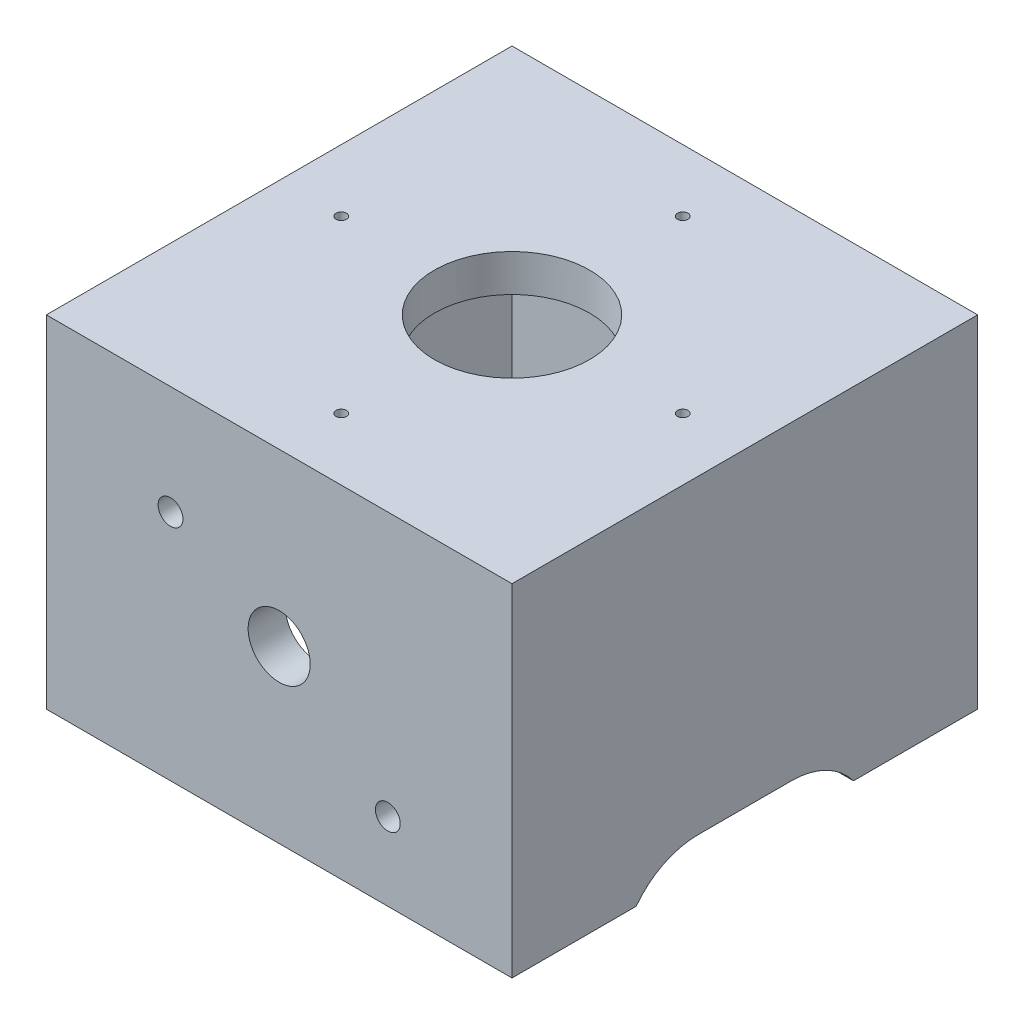
SolidWorks part; units mm, degrees
material "Teak"
ref_plane "Front Plane" through (0, 0, 0) normal (0, 0, 1) x (1, 0, 0)
ref_plane "Top Plane" through (0, 0, 0) normal (0, 1, 0) x (1, 0, 0)
ref_plane "Right Plane" through (0, 0, 0) normal (1, 0, 0) x (0, 0, -1)
sketch "Sketch1" plane through (0, 0, 0) normal (0, 1, 0) x (1, 0, 0)
  line L1 (0, 0) -> (150, 0)
  line L2 (0, 0) -> (0, 150)
  line L3 (0, 150) -> (150, 150)
  line L4 (150, 0) -> (150, 150)
  dimension "D1" = 150
  dimension "D2" = 150
extrude "Boss-Extrude1" add sketch "Sketch1" along normal blind 110
sketch "Sketch3" plane through (0, 0, 0) normal (0, -1, 0) x (1, 0, 0)
  line L14 (12, -138) -> (138, -138)
  line L15 (138, -138) -> (138, -12)
  line L16 (12, -12) -> (12, -138)
  line L17 (138, -12) -> (12, -12)
  line L18 (12, -138) -> (138, -138)
  line L19 (138, -138) -> (138, -12)
  line L20 (12, -12) -> (12, -138)
  line L21 (138, -12) -> (12, -12)
  dimension "D1" = 12
extrude "Cut-Extrude1" cut sketch "Sketch3" against normal offset from surface (98 mm away) 12 up to face at (75, 110, -75)
sketch "Sketch4" plane through (0, 110, 0) normal (0, 1, 0) x (1, 0, 0)
  line L0 (150, 0) -> (150, 150) construction
  line L1 (150, 150) -> (0, 150) construction
  line L2 (0, 150) -> (0, 0) construction
  circle A0 centre (75, 75) radius 55
  circle A1 centre (75, 130) radius 1.7
  circle A2 centre (130, 75) radius 1.7
  circle A3 centre (75, 20) radius 1.7
  circle A4 centre (20, 75) radius 1.7
  circle A5 centre (75, 75) radius 25
  point P4 (150, 75)
  point P7 (75, 150)
  point P12 (0, 75)
  dimension "D1" = 110
  dimension "D2" = 3.4
  dimension "D4" = 50
  dimension "D3" = 4
extrude "Cut-Extrude2" cut sketch "Sketch4" against normal through all contours A2 | A1 | A4 | A3 | A5
sketch "Sketch6" plane through (0, 0, 0) normal (-1, 0, 0) x (0, 0, 1)
  line L1 (0, 110) -> (0, 0) construction
  line L14 (-150, 0) -> (0, 0) construction
  line L15 (-75, 110) -> (-75, 0) construction
  line L16 (-150, 110) -> (0, 110) construction
  line L20 (-90, 10) -> (-60, 10)
  line L21 (-40, 0) -> (-110, 0)
  arc A2 (-110, 0) -> (-90, 10) centre (-90, -15) cw
  arc A3 (-40, 0) -> (-60, 10) centre (-60, -15) ccw
  dimension "D3" = 40
  dimension "D1" = 25
  dimension "D2" = 10
extrude "Cut-Extrude3" cut sketch "Sketch6" against normal through all
sketch "Sketch7" plane through (0, 0, 0) normal (0, 0, -1) x (-1, 0, 0)
  line L1 (-150, 110) -> (-150, 0) construction
  line L3 (0, 0) -> (-150, 0) construction
  line L5 (0, 110) -> (-150, 110) construction
  line L15 (-75, 110) -> (-75, 0) construction
  line L20 (-90, 10) -> (-60, 10)
  line L21 (-40, 0) -> (-110, 0)
  arc A2 (-110, 0) -> (-90, 10) centre (-90, -15) cw
  arc A3 (-40, 0) -> (-60, 10) centre (-60, -15) ccw
  point P13 (-75, 110)
  dimension "D3" = 40
  dimension "D1" = 25
  dimension "D2" = 10
extrude "Cut-Extrude4" cut sketch "Sketch7" against normal up to surface (-138 mm away) from surface up to face at (75, 49, -138) starting at face at (75, 55, -150)
sketch "Sketch5" plane through (0, 0, 0) normal (0, 0, 1) x (1, 0, 0)
  line L0 (0, 110) -> (0, 0) construction
  line L1 (150, 110) -> (150, 0) construction
  line L2 (0, 110) -> (150, 110) construction
  line L4 (75, 110) -> (75, 0) construction
  line L5 (0, 100) -> (150, 100) construction
  line L8 (0, 0) -> (150, 0) construction
  circle A0 centre (40, 75) radius 4
  circle A1 centre (75, 55) radius 10
  circle A2 centre (110, 25) radius 4
  point P13 (75, 110)
  point P14 (75, 55)
  point P15 (0, 0)
  point P16 (75, 89.7773)
  point P20 (0, 0)
  point P21 (0, 0)
  point P22 (12.515, 100)
  point P23 (0, 0)
  point P25 (0, 0)
  point P26 (0, 0)
  point P27 (0, 0)
  dimension "D1" = 8
  dimension "D2" = 20
  dimension "D3" = 8
  dimension "D4" = 40
  dimension "D5" = 40
  dimension "D6" = 25
  dimension "D7" = 25
  dimension "D8" = 10
extrude "Cut-Extrude5" cut sketch "Sketch5" against normal up to surface (12 mm away) up to face at (75, 49, -12)
